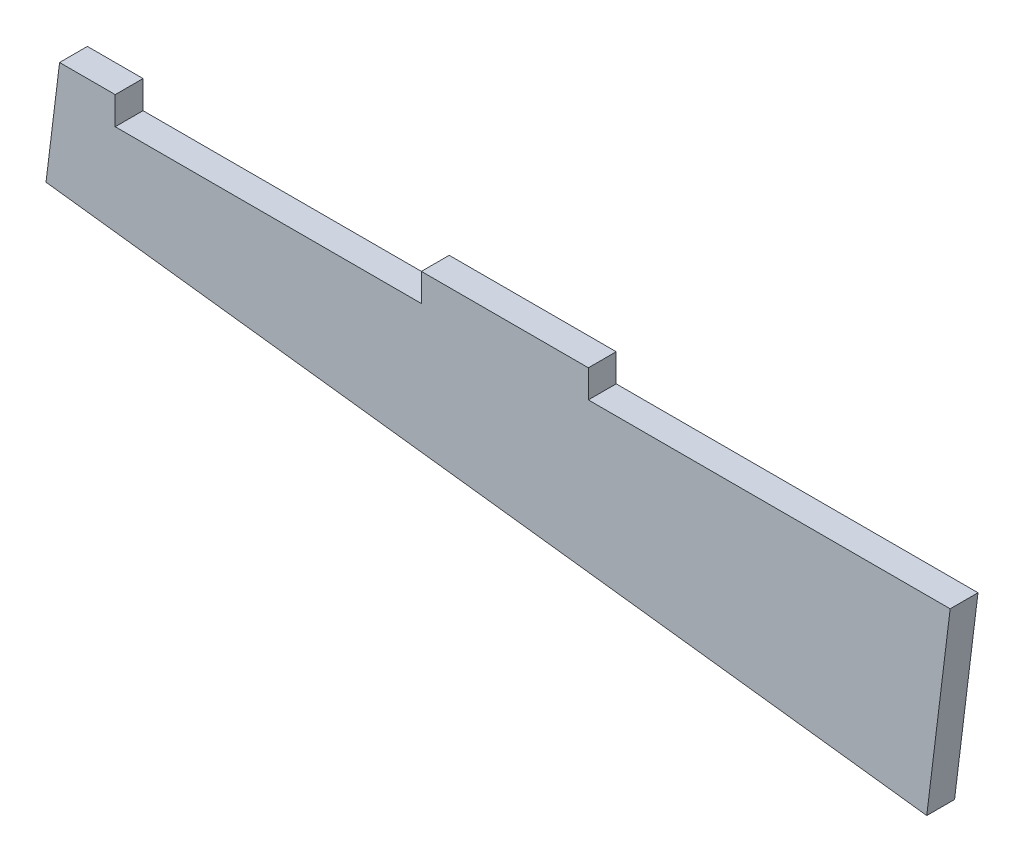
SolidWorks part; units mm, degrees
ref_plane "Front Plane" through (0, 0, 0) normal (0, 0, 1) x (1, 0, 0)
ref_plane "Top Plane" through (0, 0, 0) normal (0, 1, 0) x (1, 0, 0)
ref_plane "Right Plane" through (0, 0, 0) normal (1, 0, 0) x (0, 0, -1)
sketch "Sketch1" plane through (0, 0, 0) normal (0, 0, 1) x (1, 0, 0)
  line L0 (-195.3168, -62.6592) -> (-182.6168, -62.6592)
  line L4 (-182.6168, -62.6592) -> (-182.6168, -69.0092)
  line L5 (-182.6168, -69.0092) -> (-112.7668, -69.0092)
  line L6 (-112.7668, -69.0092) -> (-112.7668, -62.6592)
  line L7 (-112.7668, -62.6592) -> (-74.6668, -62.6592)
  line L8 (-74.6668, -62.6592) -> (-74.6668, -69.0092)
  line L9 (-74.6668, -69.0092) -> (7.8832, -69.0092)
  line L10 (7.8832, -69.0092) -> (2.5379, -112.5435)
  line L11 (2.5379, -112.5435) -> (-198.4122, -87.8699)
  line L12 (-198.4122, -87.8699) -> (-195.3168, -62.6592)
  line L13 (-360.4168, -20.6725) -> (-341.5088, -22.9941) construction
  dimension "D1" = 12.7
  dimension "D2" = 6.35
  dimension "D3" = 69.85
  dimension "D4" = 38.1
  dimension "D5" = 82.55
  dimension "D6" = 25.4
extrude "Boss-Extrude1" add sketch "Sketch1" against normal blind 6.35
sketch "Sketch2" [suppressed] plane through (0, 0, 0) normal (0, 0, 1) x (1, 0, 0)
  line L0 (-195.3168, -62.6592) -> (-74.6668, -62.6592)
  line L1 (-74.6668, -62.6592) -> (-74.6668, -69.0092)
  line L2 (-74.6668, -69.0092) -> (-196.0964, -69.0092)
  line L3 (-195.3168, -62.6592) -> (-198.4122, -87.8699) construction
  line L4 (-196.0964, -69.0092) -> (-195.3168, -62.6592)
extrude "Cut-Extrude1" [suppressed] cut sketch "Sketch2" against normal through all
